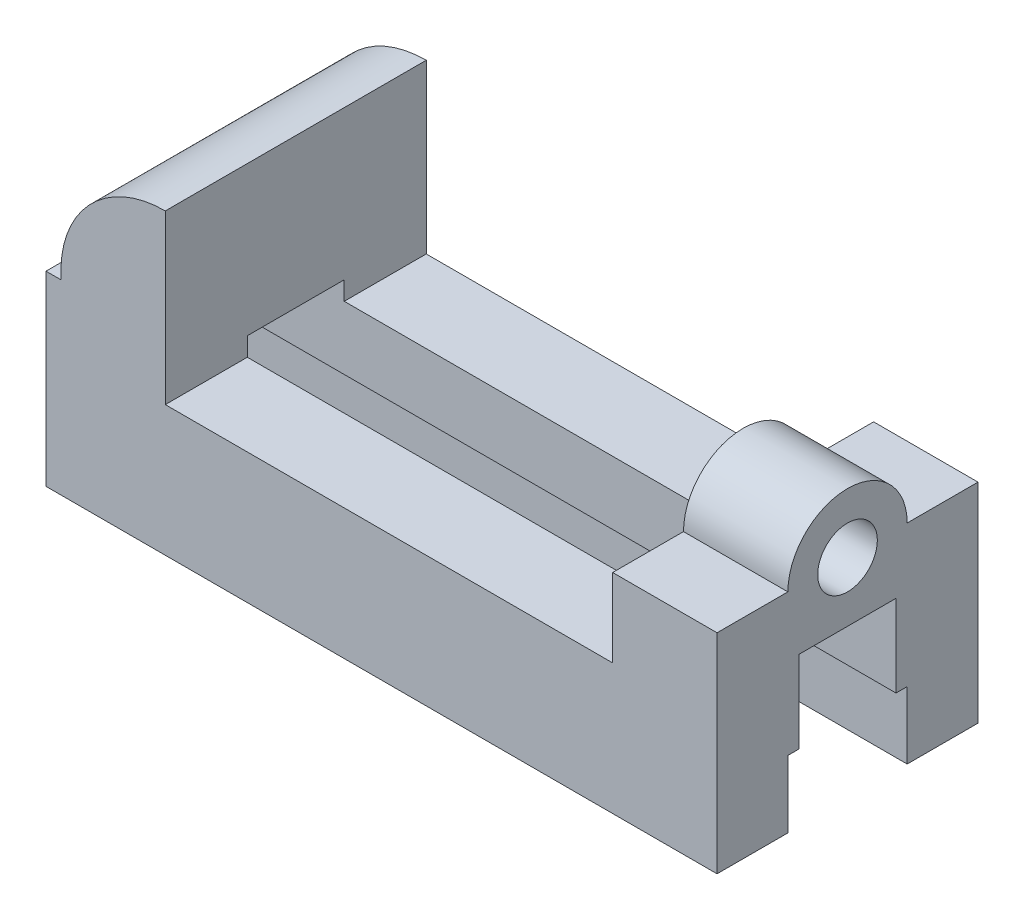
SolidWorks part; units mm, degrees
ref_plane "Front Plane" through (0, 0, 0) normal (0, 0, 1) x (1, 0, 0)
ref_plane "Top Plane" through (0, 0, 0) normal (0, 1, 0) x (1, 0, 0)
ref_plane "Right Plane" through (0, 0, 0) normal (1, 0, 0) x (0, 0, -1)
sketch "Sketch1" plane through (0, 0, 0) normal (0, 0, 1) x (1, 0, 0)
  line L0 (0, 0) -> (-89894.8654, 0) construction
  line L1 (0, 0) -> (0, -89894.8654) construction
  line L2 (0, 0) -> (180, 0)
  line L3 (180, 0) -> (180, 56)
  line L4 (180, 56) -> (152, 56)
  line L5 (152, 56) -> (152, 35)
  line L6 (152, 35) -> (32, 35)
  line L7 (32, 35) -> (32, 80)
  line L8 (4.0715, 50) -> (0, 50)
  line L9 (0, 50) -> (0, 0)
  arc A0 (32, 80) -> (4.0715, 50) centre (32, 52) ccw
  point P2 (5.0932, 0.6416)
  point P5 (18.6384, 43.5872)
  point P16 (0, 0)
  point P17 (24.2402, 1.7872)
  point P19 (10.0027, 25.0254)
  point P20 (7.1041, 0)
  point P21 (0, 38.8141)
  dimension "D1" = 180
  dimension "D6" = 28
  dimension "D2" = 56
  dimension "D3" = 28
  dimension "D4" = 21
  dimension "D5" = 80
  dimension "D7" = 50
  dimension "D8" = 32
extrude "Boss-Extrude1" add sketch "Sketch1" along normal mid plane 70
sketch "Sketch2" plane through (0, 0, 0) normal (-1, 0, 0) x (0, 0, 1)
  line L0 (-16, 0) -> (-16, 18)
  line L1 (35, 0) -> (-35, 0) construction
  line L2 (-16, 18) -> (-13, 18)
  line L3 (-13, 18) -> (-13, 40)
  line L4 (-13, 40) -> (13, 40)
  line L5 (13, 40) -> (13, 18)
  line L6 (13, 18) -> (16, 18)
  line L7 (16, 18) -> (16, 0)
  line L8 (16, 0) -> (-16, 0)
  line L9 (0, 0) -> (48172.154, 0) construction
  line L10 (0, 0) -> (0, -50000) construction
  line L11 (-35, 50) -> (-35, 0) construction
  line L13 (35, 50) -> (35, 0) construction
  dimension "D1" = 18
  dimension "D2" = 22
  dimension "D3" = 19
  dimension "D4" = 19
  dimension "D5" = 26
extrude "Cut-Extrude1" cut sketch "Sketch2" against normal through all
sketch "Sketch3" plane through (180, 0, 0) normal (1, 0, 0) x (0, 0, -1)
  line L0 (-35, 56) -> (35, 56) construction
  circle A0 centre (0, 56) radius 8
  circle A1 centre (0, 56) radius 16
  line M6 (35, 56) -> (-35, 56)
  dimension "D1" = 16
  dimension "D2" = 32
extrude "Boss-Extrude2" add sketch "Sketch3" against normal up to surface (28 mm away) up to face at (152, 41.5, 0)
extrude "Cut-Extrude2" cut sketch "Sketch3<2>" against normal up to next contours A0 M6 region at (180, 52.6047, 0)
sketch "Sketch3<2>" plane through (180, 0, 0) normal (1, 0, 0) x (0, 0, -1) same geometry as "Sketch3"
